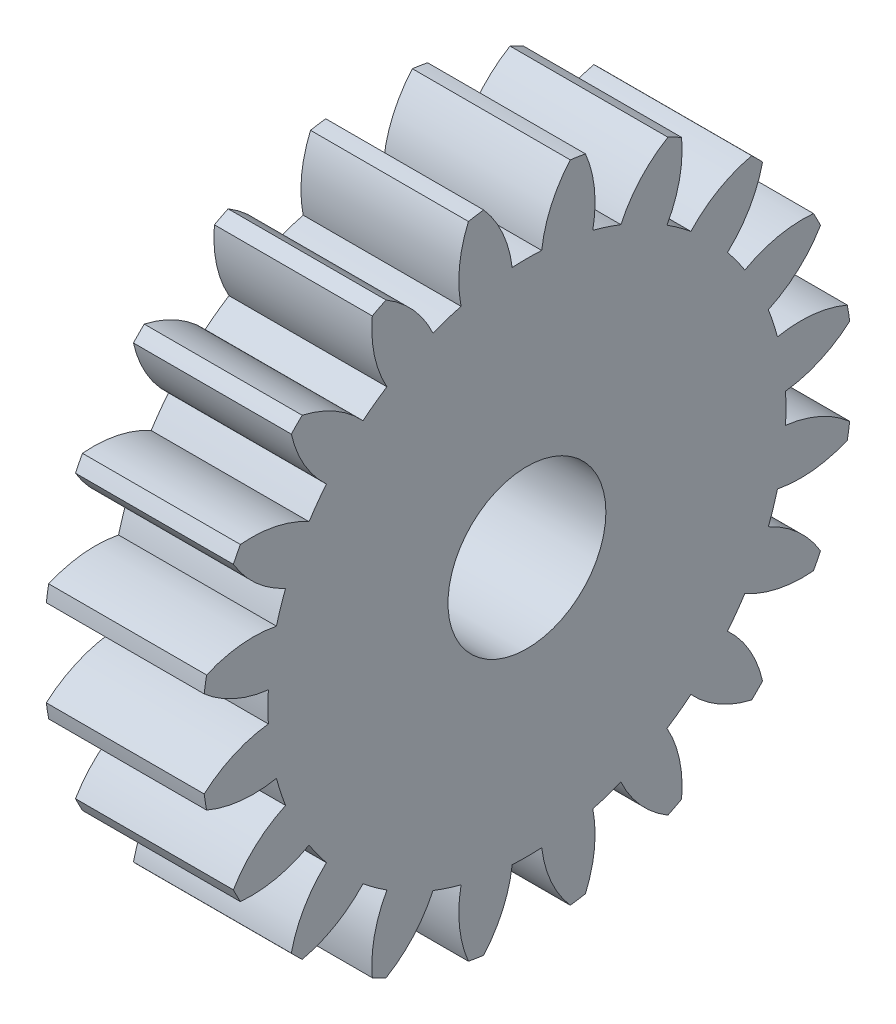
SolidWorks part; units mm, degrees
ref_plane "Plane1" through (0, 0, 0) normal (0, 0, 1) x (1, 0, 0)
ref_plane "Plane2" through (0, 0, 0) normal (0, 1, 0) x (1, 0, 0)
ref_plane "Plane3" through (0, 0, 0) normal (1, 0, 0) x (0, 0, -1)
sketch "HoldingSke" plane through (0, 0, 0) normal (0, 1, 0) x (1, 0, 0)
  line L0 (0, 0) -> (0.8353, -0.304)
  line L1 (-15, 0) -> (100, 0) construction
  line L2 (0, 0) -> (-2.1039, 2.3779)
  line L3 (0, 0) -> (-11.863, 4.5341)
  line L4 (0, 0) -> (8.1152, 2.9537)
  line L5 (0, 0) -> (-46.8476, -17.4728)
  line L6 (0, 0) -> (-4.9738, -3.3558)
  line L7 (-2.1039, 2.3779) -> (8.6586, 51.2059)
  line L8 (-76.2, 54.61) -> (-75.2, 54.61)
  line L9 (-71.009, 38.7566) -> (-53.1078, 45.2721)
  line L10 (-76.2, 71.12) -> (104.1128, 71.12)
  line L11 (0, 0) -> (-6, 0)
  line L12 (-76.2, 101.6) -> (-76.158, 101.6)
  line L13 (24.9733, 27.94) -> (52.9518, 28.4284)
  line L14 (24.9733, 27.94) -> (24.9743, 27.94)
  line L15 (24.9733, 27.94) -> (100.4006, 29.5858)
  line L16 (-63.627, -1.125) -> (-12.827, -1.125)
  circle A0 centre (0, 0) radius 3
  circle A1 centre (0, 0) radius 9.8427
  circle A2 centre (0, 0) radius 37.5
  circle A3 centre (0, 0) radius 3
  dimension "MHD" = 19.6855
  dimension "Hub_dia" = 75
  dimension "Bore" = 6
  dimension "MBD" = 6
  dimension "Num_teeth" = 20
  dimension "Pitch" = 0.8889
  dimension "Overall_len" = 50
  dimension "Show_teeth" = 20
  dimension "Thickness" = 6
  dimension "OAL" = 50.0001
  dimension "T_dim" = 1
  dimension "Ap" = 20
  dimension "H" = 19.05
  dimension "Pitch_radius" = 180.3128
  dimension "Width" = 6
  dimension "Backlash" = 0.042
  dimension "Addendum_fac" = 1
  dimension "Dedendum_fac" = 1.25
  dimension "Clearance_fac" = 0.25
  dimension "Dedendum_add" = 0.001
  dimension "Module" = 1.125
sketch "BasProSke" plane through (0, 0, 0) normal (0, 1, 0) x (1, 0, 0)
  line L0 (-10, 0) -> (60, 0) construction
  line L1 (0, 0) -> (0, 12.375)
  line L2 (0, 0) -> (6, 0)
  line L3 (6, 0) -> (6, 12.375)
  line L4 (6, 12.375) -> (0, 12.375)
  dimension "Thickness" = 6
  dimension "Diameter" = 24.75
revolve "Base-Revolve" add sketch "BasProSke" angle 360 about L0
sketch "TooCutSke" plane through (0, 0, 0) normal (1, 0, 0) x (0, 0, -1)
  line L1 (0, 0) -> (0, 107) construction
  line L2 (0, 0) -> (-0.9561, 11.2093) construction
  line L3 (0, 0) -> (-3.5107, 22.1654) construction
  line L4 (-0.9561, 11.2093) -> (-1.7553, 11.0827) construction
  arc A0 (0.5613, 9.8267) -> (-0.5613, 9.8267) centre (0, 0) ccw
  arc A1 (1.6669, 12.2879) -> (-1.6669, 12.2879) centre (0, 0) ccw
  circle A2 centre (0, 0) radius 11.25 construction
  circle A3 centre (0, 0) radius 10.5715 construction
  arc A4 (-0.5613, 9.8267) -> (-1.6669, 12.2879) centre (-5.0301, 9.2981) ccw
  arc A5 (1.6669, 12.2879) -> (0.5613, 9.8267) centre (5.0301, 9.2981) ccw
  dimension "Root_dia" = 19.6855
  dimension "Overcut_dia" = 24.8008
  dimension "Pitch_dia" = 22.5
  dimension "Base_dia" = 21.1431
  dimension "Flank_rad" = 4.5
  dimension "Half_ang" = 9
  dimension "Half_CT" = 0.8092
extrude "ToothCut" cut sketch "TooCutSke" along normal through all
fillet "Breaks" [suppressed] radius 0.0225 tangent propagation no
fillet "RootFillets" [suppressed] radius 0.2823
pattern_circular "TeethCuts" count 20 over 360 about axis through (-10, 0, 0) along (1, 0, 0) of "ToothCut", "RootFillets", "Breaks"
sketch "HubNeaOneSke" plane through (0, 0, 0) normal (-1, 0, 0) x (0, 0, 1)
  circle A0 centre (0, 0) radius 9.8427
  dimension "Diameter" = 19.6855
extrude "HubNearOne" [suppressed] add sketch "HubNeaOneSke" along normal blind 44.0001
sketch "HubNeaBotSke" plane through (0, 0, 0) normal (-1, 0, 0) x (0, 0, 1)
  circle A0 centre (0, 0) radius 9.8427
  dimension "Diameter" = 19.6855
extrude "HubNearBoth" [suppressed] add sketch "HubNeaBotSke" along normal blind 22
ref_plane "FarPln" through (6, 0, 0) normal (1, 0, 0) x (0, 0, -1)
sketch "HubFarSke" plane through (6, 0, 0) normal (1, 0, 0) x (0, 0, -1)
  circle A0 centre (0, 0) radius 9.8427
  dimension "Diameter" = 19.6855
extrude "HubFar" [suppressed] add sketch "HubFarSke" along normal blind 22
sketch "BorSke" plane through (0, 0, 0) normal (1, 0, 0) x (0, 0, -1)
  circle A0 centre (0, 0) radius 3
  dimension "Diameter" = 6
extrude "Bore" cut sketch "BorSke" along normal mid plane 100.0001
sketch "KeySke" plane through (0, 0, 0) normal (1, 0, 0) x (0, 0, -1)
  line L0 (-1, 0) -> (-1, 4)
  line L1 (-1, 4) -> (1, 4)
  line L2 (1, 4) -> (1, 0)
  line L3 (0, 0) -> (0, 34) construction
  line L4 (-1, 0) -> (1, 0)
  dimension "Offset" = 4
  dimension "Width" = 2
extrude "Keyway" [suppressed] cut sketch "KeySke" along normal mid plane 100.0001
pattern_circular "Keyway2" [suppressed] count 2 every 90 about axis through (-10, 0, 0) along (1, 0, 0) reverse direction yes
sketch "Sketch1" plane through (6, 0, 0) normal (1, 0, 0) x (0, 0, -1)
  circle A0 centre (0, 0) radius 3 construction
  circle A1 centre (0, 0) radius 3
extrude "Boss-Extrude1" add sketch "Sketch1" against normal up to surface (6 mm away) up to face at (0, 0, -3)
sketch "Sketch2" plane through (6, 0, 0) normal (1, 0, 0) x (0, 0, -1)
  line L0 (-1.8, 2.0125) -> (-1.8, -2.0125)
  line L1 (1.8, 2.0125) -> (1.8, -2.0125)
  line L2 (-1.8, 0) -> (1.8, 0) construction
  circle A0 centre (0, 0) radius 2.7
  point P9 (0, 0)
  dimension "D1" = 5.4
  dimension "D2" = 3.6
extrude "Cut-Extrude1" cut sketch "Sketch2" against normal up to surface (6 mm away) contours L0 L2 L1 A0 | L2 L0 A0 L1 region at (6, 1.25, 0) region at (6, -1.25, 0) up to face at (0, 0, 0)
sketch "Sketch3" plane through (6, 0, 0) normal (1, 0, 0) x (0, 0, -1)
  circle A0 centre (0, 0) radius 3
  dimension "D1" = 6
extrude "Cut-Extrude2" cut sketch "Sketch3" against normal up to surface (6 mm away) up to face at (0, 0, 0)
equation "' \"Module@HoldingSke\" = 6.35"
equation "' \"Num_teeth@HoldingSke\" = 12"
equation "' \"Ap@HoldingSke\" =  20"
equation "' \"Ap@HoldingSke\" = 20"
equation "' \"Width@HoldingSke\" = 0.5 * 25.4"
equation "' \"Hub_dia@HoldingSke\"= 1 * 25.4"
equation "' \"Hub_dia@HoldingSke\" = 1 * 25.4"
equation "' \"Overall_len@HoldingSke\" = 1.0 * 25.4"
equation "' \"Bore@HoldingSke\" = 0.75 * 25.4"
equation "' \"T_dim@HoldingSke\" = 0.1 * 25.4"
equation "' \"Width@KeySke\" = 0.25 * 25.4"
equation "' \"Show_teeth@HoldingSke\" = 13"
equation "' \"Backlash@HoldingSke\" = 0.009 * 25.4"
equation "' \"Addendum_fac@HoldingSke\" = 1.0"
equation "' \"Dedendum_fac@HoldingSke\" = 1.25"
equation "' \"Dedendum_add@HoldingSke\" = 0.00005 * 25.4"
equation "' \"Clearance_fac@HoldingSke\" = 0.25"
equation "\"Pitch@HoldingSke\" = 1 / \"Module@HoldingSke\""
equation "\"Overcut_dia@TooCutSke\" = (\"Num_teeth@HoldingSke\" + 2 * \"Addendum_fac@HoldingSke\") / \"Pitch@HoldingSke\" + 0.002 * 25.4"
equation "\"Pitch_dia@TooCutSke\" = \"Num_teeth@HoldingSke\" / \"Pitch@HoldingSke\""
equation "\"Base_dia@TooCutSke\" = \"Num_teeth@HoldingSke\" / \"Pitch@HoldingSke\" * cos((\"Ap@HoldingSke\"  * 3.14159265 / 180))"
equation "\"Root_dia@TooCutSke\" = (\"Num_teeth@HoldingSke\" + 2) / \"Pitch@HoldingSke\" - 2 * (\"Addendum_fac@HoldingSke\" + \"Dedendum_fac@HoldingSke\") / \"Pitch@HoldingSke\" - \"Dedendum_add@HoldingSke\" * 2"
equation "\"Half_ang@TooCutSke\" = 180 / \"Num_teeth@HoldingSke\""
equation "\"Half_CT@TooCutSke\" = \"Num_teeth@HoldingSke\" / \"Pitch@HoldingSke\" * sin((3.14159265 / 2 / \"Num_teeth@HoldingSke\")) / 2 - 7 * \"Backlash@HoldingSke\" / 4"
equation "\"Flank_rad@TooCutSke\" = \"Num_teeth@HoldingSke\" / \"Pitch@HoldingSke\" / 5"
equation "\"Radius@RootFillets\" = \"Clearance_fac@HoldingSke\" / \"Pitch@HoldingSke\" + \"Dedendum_add@HoldingSke\""
equation "\"Break_rad@Breaks\" = 0.02 / \"Pitch@HoldingSke\""
equation "\"Thickness@HoldingSke\" = \"Width@HoldingSke\""
equation "\"OAL@HoldingSke\" = \"Thickness@HoldingSke\""
equation "\"MHD@HoldingSke\" = (\"Num_teeth@HoldingSke\" + 2) / \"Pitch@HoldingSke\" - 2 * (\"Addendum_fac@HoldingSke\" + \"Dedendum_fac@HoldingSke\")  / \"Pitch@HoldingSke\" - \"Dedendum_add@HoldingSke\" * 2"
equation "\"MBD@HoldingSke\" = (\"Num_teeth@HoldingSke\" + 2) / \"Pitch@HoldingSke\" - 2 * (\"Addendum_fac@HoldingSke\" + \"Dedendum_fac@HoldingSke\")  / \"Pitch@HoldingSke\" - \"Dedendum_add@HoldingSke\" * 2 - 0.002 * 25.4"
equation "\"MHD@HoldingSke\" = ((sgn( \"MHD@HoldingSke\" - \"Hub_dia@HoldingSke\" )-1)*( \"MHD@HoldingSke\" - \"Hub_dia@HoldingSke\" ))/-2+ \"Hub_dia@HoldingSke\""
equation "\"MBD@HoldingSke\" = ((sgn( \"MBD@HoldingSke\" - \"Bore@HoldingSke\" )-1)*( \"MBD@HoldingSke\" - \"Bore@HoldingSke\" ))/-2+ \"Bore@HoldingSke\""
equation "\"OAL@HoldingSke\" = ((sgn( \"OAL@HoldingSke\" - \"Overall_len@HoldingSke\" )+1)*( \"OAL@HoldingSke\" - \"Overall_len@HoldingSke\" ))/2 + \"Overall_len@HoldingSke\" + 0.000002 * 25.4"
equation "\"Num_teeth@TeethCuts\" = int( \"Show_teeth@HoldingSke\" ) + 1"
equation "\"Num_teeth@TeethCuts\" = ((sgn( \"Num_teeth@TeethCuts\" - \"Num_teeth@HoldingSke\" )-1)*( \"Num_teeth@TeethCuts\" - \"Num_teeth@HoldingSke\" ))/-2+ \"Num_teeth@HoldingSke\""
equation "\"Num_teeth@TeethCuts\" = ((sgn( \"Num_teeth@TeethCuts\" - 2.0)+1)*( \"Num_teeth@TeethCuts\" - 2.0))/2 +2.0"
equation "\"Angle@TeethCuts\" = 360.0 / \"Num_teeth@HoldingSke\""
equation "\"Diameter@BasProSke\" = (\"Num_teeth@HoldingSke\" + 2 * \"Addendum_fac@HoldingSke\") / \"Pitch@HoldingSke\""
equation "\"Thickness@BasProSke\"  = \"Thickness@HoldingSke\""
equation "' \"Fillet_rad@BasProSke\" =  \"Thickness@HoldingSke\" * 0.05"
equation "' \"Fillet_rad@BasProSke\" = \"Thickness@HoldingSke\" * 0.05"
equation "\"MHD@HoldingSke\" = ((sgn( \"MHD@HoldingSke\" - \"Root_dia@TooCutSke\" )-1)*( \"MHD@HoldingSke\" - \"Root_dia@TooCutSke\" ))/-2+ \"Root_dia@TooCutSke\""
equation "\"Diameter@HubNeaOneSke\" = \"MHD@HoldingSke\""
equation "\"Length@HubNearOne\" = \"OAL@HoldingSke\" - \"Thickness@BasProSke\""
equation "\"Diameter@HubNeaBotSke\" = \"MHD@HoldingSke\""
equation "\"Length@HubNearBoth\" = ( \"OAL@HoldingSke\" - \"Thickness@BasProSke\" ) / 2.0"
equation "\"Thickness@FarPln\" = \"Thickness@BasProSke\""
equation "\"Diameter@HubFarSke\" = \"MHD@HoldingSke\""
equation "\"Length@HubFar\" = ( \"OAL@HoldingSke\" - \"Thickness@BasProSke\" ) / 2.0"
equation "\"Diameter@BorSke\" = \"MBD@HoldingSke\""
equation "\"D1@Bore\" = \"OAL@HoldingSke\" * 2.0"
equation "\"D1@Keyway\" = \"OAL@HoldingSke\" * 2.0"
equation "\"Offset@KeySke\" = \"T_dim@HoldingSke\" + \"MBD@HoldingSke\" / 2.0"
